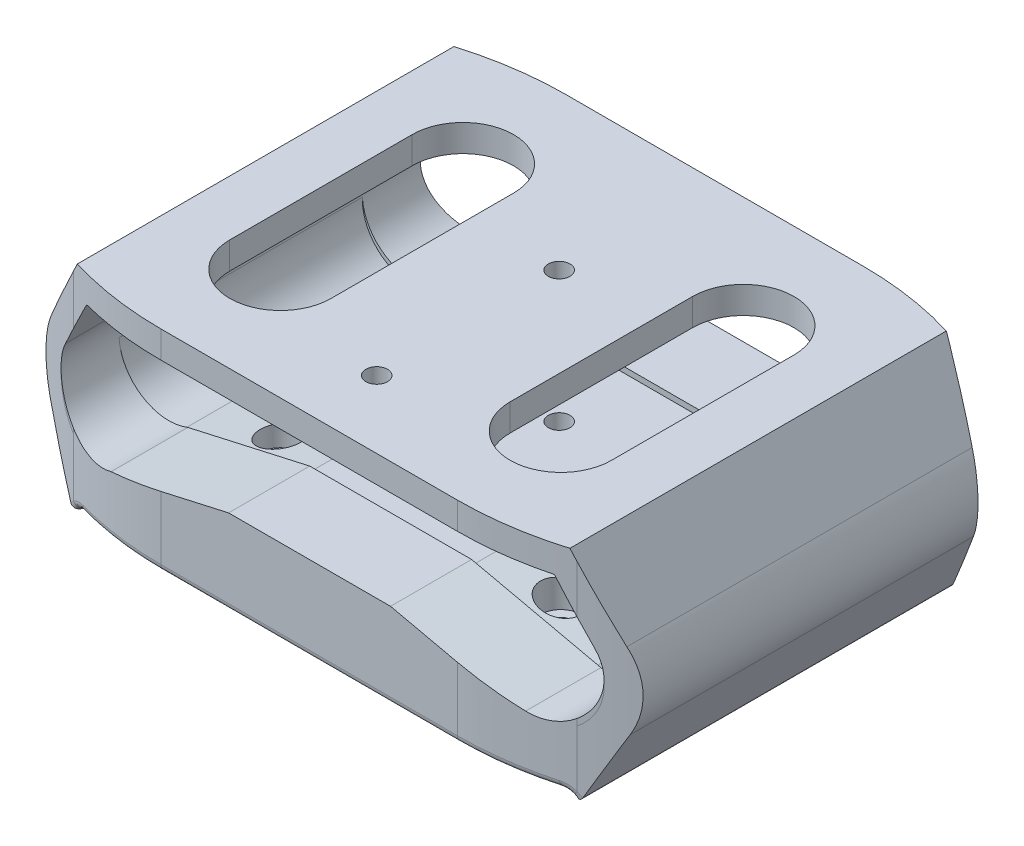
SolidWorks part; units mm, degrees
ref_plane "前视基准面" through (0, 0, 0) normal (0, 0, 1) x (1, 0, 0)
ref_plane "上视基准面" through (0, 0, 0) normal (0, 1, 0) x (1, 0, 0)
ref_plane "右视基准面" through (0, 0, 0) normal (1, 0, 0) x (0, 0, -1)
sketch "草图1" plane through (0, 0, 0) normal (0, 0, 1) x (1, 0, 0)
  line L6 (-36.4384, 98.3864) -> (-42.625, 87.564)
  line L10 (42.5656, 87.668) -> (36.4384, 98.3864)
  line L11 (36.4384, 98.3864) -> (-36.4384, 98.3864)
  line L12 (-34.1176, 94.3864) -> (-39.1524, 85.5789)
  line L13 (-31.105, 74.6866) -> (-11.9778, 78.9864)
  line L14 (-11.9778, 78.9864) -> (11.9778, 78.9864)
  line L15 (11.9778, 78.9864) -> (30.0087, 74.933)
  line L16 (39.118, 85.639) -> (34.1176, 94.3864)
  line L17 (34.1176, 94.3864) -> (-34.1176, 94.3864)
  line L18 (-34.1176, 94.3864) -> (-39.1524, 85.5789)
  line L19 (-31.105, 74.6866) -> (-11.9778, 78.9864)
  line L20 (-11.9778, 78.9864) -> (11.9778, 78.9864)
  line L21 (11.9778, 78.9864) -> (30.0087, 74.933)
  line L22 (39.118, 85.639) -> (34.1176, 94.3864)
  line L23 (34.1176, 94.3864) -> (-34.1176, 94.3864)
  line L24 (35, 67.1864) -> (21.943, 67.1864) construction
  line L25 (-21.943, 67.1864) -> (21.943, 67.1864) construction
  line L26 (-21.943, 67.1864) -> (-35, 67.1864) construction
  line L27 (35, 67.1864) -> (21.943, 67.1864)
  line L28 (-21.943, 67.1864) -> (21.943, 67.1864)
  line L29 (-21.943, 67.1864) -> (-35, 67.1864)
  line L30 (-37, 65.1864) -> (-42.8843, 76.7286)
  line L31 (37, 65.1864) -> (42.908, 76.5149)
  line L33 (-30.2277, 70.7839) -> (-11.5337, 74.9864) construction
  line L34 (-11.5337, 74.9864) -> (11.5337, 74.9864) construction
  line L35 (11.5337, 74.9864) -> (28.8425, 71.0953) construction
  arc A2 (-42.625, 87.564) -> (-42.8843, 76.7286) centre (-32.728, 81.9064) ccw
  arc A3 (42.908, 76.5149) -> (42.5656, 87.668) centre (32.8, 81.7864) ccw
  arc A4 (-39.1524, 85.5789) -> (-31.105, 74.6866) centre (-32.728, 81.9064) ccw
  arc A5 (30.0087, 74.933) -> (39.118, 85.639) centre (32.8, 81.7864) ccw
  arc A6 (-39.1524, 85.5789) -> (-31.105, 74.6866) centre (-32.728, 81.9064) ccw
  arc A7 (30.0087, 74.933) -> (39.118, 85.639) centre (32.8, 81.7864) ccw
  arc A8 (37, 65.1864) -> (35, 67.1864) centre (35, 65.1864) ccw construction
  arc A9 (-35, 67.1864) -> (-37, 65.1864) centre (-35, 65.1864) ccw construction
  arc A10 (37, 65.1864) -> (35, 67.1864) centre (35, 65.1864) ccw
  arc A11 (-35, 67.1864) -> (-37, 65.1864) centre (-35, 65.1864) ccw
  arc A12 (-42.625, 87.564) -> (-30.2277, 70.7839) centre (-32.728, 81.9064) ccw construction
  arc A13 (28.8425, 71.0953) -> (42.5656, 87.668) centre (32.8, 81.7864) ccw construction
  dimension "D1" = 0.2
  dimension "D2" = 4
extrude "凸台-拉伸1" add sketch "草图1" against normal up to surface (60 mm away)
sketch "草图2" plane through (0, 67.1864, 0) normal (0, -1, 0) x (1, 0, 0)
  line L1 (46.1297, -53.7608) -> (54.661, -49.0455) construction
  line L2 (46.1297, -53.7608) -> (54.661, -49.0455)
  line L3 (35, -60) -> (-35, -60) construction
  line L4 (21.943, -58) -> (21.943, -60) construction
  line L5 (54.661, -49.0455) -> (55.2201, -72.0519)
  line L6 (55.2201, -72.0519) -> (47.4236, -78.506)
  line L7 (47.4236, -78.506) -> (21.943, -68.9024)
  line L8 (21.943, -68.9024) -> (21.943, -60)
  line L12 (-47.4236, -78.506) -> (-21.943, -68.9024)
  line L13 (-55.2201, -72.0519) -> (-47.4236, -78.506)
  line L14 (-54.661, -49.0455) -> (-55.2201, -72.0519)
  line L15 (-46.1297, -53.7608) -> (-54.661, -49.0455)
  line L16 (-21.943, -68.9024) -> (-21.943, -60)
  line L19 (-55.2201, 12.0519) -> (-47.4236, 18.506)
  line L20 (-54.661, -10.9545) -> (-55.2201, 12.0519)
  line L21 (-46.1297, -6.2392) -> (-54.661, -10.9545)
  line L22 (-21.943, 8.9024) -> (-21.943, 0)
  line L23 (-47.4236, 18.506) -> (-21.943, 8.9024)
  line L24 (47.4236, 18.506) -> (21.943, 8.9024)
  line L25 (55.2201, 12.0519) -> (47.4236, 18.506)
  line L26 (54.661, -10.9545) -> (55.2201, 12.0519)
  line L27 (46.1297, -6.2392) -> (54.661, -10.9545)
  line L28 (21.943, 8.9024) -> (21.943, 0)
  arc A0 (37.2486, -57.5998) -> (21.943, -60) centre (21.943, -10) cw
  arc A1 (-37.2486, -57.5998) -> (-21.943, -60) centre (-21.943, -10) ccw
  arc A2 (-37.2486, -2.4002) -> (-21.943, 0) centre (-21.943, -50) cw
  arc A3 (37.2486, -2.4002) -> (21.943, 0) centre (21.943, -50) ccw
  spline S0 degree 3 poles (-1285.9943, 1433.6768) (-243.3632, -0.9152) (-26.08, -85.4419) (135.79, -14.9664) (-55.3237, 244.096) (509.0811, -1999.3449) knots -22.492359 -22.492359 -22.492359 -22.492359 0.5 0.5 32.253699 32.253699 32.253699 32.253699 only from (37.2486, -57.5998) to (46.1297, -53.7608) construction
  spline S1 degree 3 poles (37.2486, -57.5998) (38.8751, -57.0768) (40.4241, -56.4871) (43.3808, -55.1998) (44.7885, -54.502) (46.1297, -53.7608) knots 0 0 0 0 0.5 0.5 1 1 1 1
  spline S2 degree 3 poles (-37.2486, -57.5998) (-38.8751, -57.0768) (-40.4241, -56.4871) (-43.3808, -55.1998) (-44.7885, -54.502) (-46.1297, -53.7608) knots 0 0 0 0 0.5 0.5 1 1 1 1
  spline S3 degree 3 poles (-37.2486, -2.4002) (-38.8751, -2.9232) (-40.4241, -3.5129) (-43.3808, -4.8002) (-44.7885, -5.498) (-46.1297, -6.2392) knots 0 0 0 0 0.5 0.5 1 1 1 1
  spline S4 degree 3 poles (37.2486, -2.4002) (38.8751, -2.9232) (40.4241, -3.5129) (43.3808, -4.8002) (44.7885, -5.498) (46.1297, -6.2392) knots 0 0 0 0 0.5 0.5 1 1 1 1
extrude "切除-拉伸1" cut sketch "草图2" against normal mid plane 138
fillet "圆角1" radius 1 12 edges at (33.7286, 63.6425, -58.5912) (28.5289, 67.1864, -59.5644) (0, 67.1864, -60) (-36.4206, 66.5942, -57.8581) (33.5845, 63.7735, -1.3741) (28.5289, 67.1864, -0.4356) (0, 67.1864, 0) (-28.5289, 67.1864, -0.4356) (-28.5289, 67.1864, -59.5644) (37, 65.1864, -30) (-37, 65.1864, -30) (-36.7035, 66.2343, -2.2284)
sketch "草图4" plane through (0, 98.3864, 0) normal (0, 1, 0) x (1, 0, 0)
  line L0 (-20.7462, 43.5) -> (-20.7462, 16.5) construction
  line L1 (-13.2462, 43.5) -> (-13.2462, 16.5)
  line L2 (-28.2462, 43.5) -> (-28.2462, 16.5)
  line L3 (0, 66.5679) -> (0, 53.4321) construction
  line L4 (20.7462, 43.5) -> (20.7462, 16.5) construction
  line L5 (13.2462, 43.5) -> (13.2462, 16.5)
  line L6 (28.2462, 43.5) -> (28.2462, 16.5)
  arc A0 (-13.2462, 43.5) -> (-28.2462, 43.5) centre (-20.7462, 43.5) ccw
  arc A1 (-28.2462, 16.5) -> (-13.2462, 16.5) centre (-20.7462, 16.5) ccw
  arc A2 (13.2462, 43.5) -> (28.2462, 43.5) centre (20.7462, 43.5) cw
  arc A3 (28.2462, 16.5) -> (13.2462, 16.5) centre (20.7462, 16.5) cw
  point P4 (-20.7462, 30)
  point P13 (20.7462, 30)
extrude "切除-拉伸2" cut sketch "草图4" against normal blind 8
sketch "草图5" plane through (0, 98.3864, 0) normal (0, 1, 0) x (1, 0, 0)
  circle A0 centre (-20.7462, 43.5) radius 1.6
  circle A1 centre (-20.7462, 16.5) radius 1.6
  circle A2 centre (20.7462, 43.5) radius 1.6
  circle A3 centre (20.7462, 16.5) radius 1.6
extrude "切除-拉伸3" cut sketch "草图5" against normal blind 80
sketch "草图6" plane through (0, 98.3864, 0) normal (0, 1, 0) x (1, 0, 0)
  circle A0 centre (-20.7462, 43.5) radius 3
  circle A1 centre (20.7462, 43.5) radius 3
  circle A2 centre (-20.7462, 16.5) radius 3
  circle A3 centre (20.7462, 16.5) radius 3
extrude "切除-拉伸4" cut sketch "草图6" against normal blind 25
sketch "草图7" plane through (0, 98.3864, 0) normal (0, 1, 0) x (1, 0, 0)
  circle A0 centre (0, 37) radius 1.6
  circle A1 centre (0, 10) radius 1.6
extrude "切除-拉伸5" cut sketch "草图7" against normal blind 36
sketch "草图8" plane through (0, 0, 0) normal (0, 0, 1) x (1, 0, 0)
  line L0 (39.2149, 86.4342) -> (34.6646, 94.3864)
  line L1 (34.6646, 94.3864) -> (-34.5297, 94.3864)
  line L2 (-34.5297, 94.3864) -> (-39.0555, 86.4616)
  line L3 (-29.9417, 75.7594) -> (-11.9125, 79.8203)
  line L4 (-11.9125, 79.8203) -> (12.0431, 79.8303)
  line L5 (12.0431, 79.8303) -> (31.1721, 75.5385)
  arc A0 (-39.0555, 86.4616) -> (-40.1359, 82.6116) centre (-32.7359, 82.6116) ccw
  arc A1 (-40.1359, 82.6116) -> (-29.9417, 75.7594) centre (-32.7359, 82.6116) ccw
  arc A2 (31.1721, 75.5385) -> (39.2149, 86.4342) centre (32.7921, 82.759) ccw
extrude "切除-拉伸6" cut sketch "草图8" against normal mid plane 184
sketch "草图9" plane through (0, 0, 0) normal (0, 0, 1) x (1, 0, 0)
  line L15 (-29.9417, 75.7594) -> (-11.9125, 79.8203)
  line L16 (-11.9125, 79.8203) -> (12.0431, 79.8303)
  line L17 (12.0431, 79.8303) -> (31.1721, 75.5385)
  line L18 (30.0087, 74.933) -> (21.943, 76.7462) construction
  line L19 (11.9778, 78.9864) -> (21.943, 76.7462) construction
  line L20 (-11.9778, 78.9864) -> (11.9778, 78.9864) construction
  line L21 (-21.943, 76.7462) -> (-11.9778, 78.9864) construction
  line L22 (-21.943, 76.7462) -> (-31.105, 74.6866) construction
  line L23 (30.0087, 74.933) -> (21.943, 76.7462)
  line L24 (11.9778, 78.9864) -> (21.943, 76.7462)
  line L25 (-11.9778, 78.9864) -> (11.9778, 78.9864)
  line L26 (-21.943, 76.7462) -> (-11.9778, 78.9864)
  line L27 (-21.943, 76.7462) -> (-31.105, 74.6866)
  arc A7 (-40.1231, 82.1763) -> (-29.9417, 75.7594) centre (-32.7359, 82.6116) ccw
  arc A8 (31.1721, 75.5385) -> (40.1798, 82.333) centre (32.7921, 82.759) ccw
  arc A9 (37.2486, 75.8728) -> (40.1798, 82.333) centre (32.8, 81.7864) ccw construction
  arc A10 (30.0087, 74.933) -> (37.2486, 75.8728) centre (32.8, 81.7864) ccw construction
  arc A11 (-37.2486, 76.0477) -> (-31.105, 74.6866) centre (-32.728, 81.9064) ccw construction
  arc A12 (-40.1231, 82.1763) -> (-37.2486, 76.0477) centre (-32.728, 81.9064) ccw construction
  arc A13 (37.2486, 75.8728) -> (40.1798, 82.333) centre (32.8, 81.7864) ccw
  arc A14 (30.0087, 74.933) -> (37.2486, 75.8728) centre (32.8, 81.7864) ccw
  arc A15 (-37.2486, 76.0477) -> (-31.105, 74.6866) centre (-32.728, 81.9064) ccw
  arc A16 (-40.1231, 82.1763) -> (-37.2486, 76.0477) centre (-32.728, 81.9064) ccw
extrude "凸台-拉伸2" add sketch "草图9" against normal blind 12
ref_plane "基准面1" through (0, 0, -30) normal (0, 0, 1) x (1, 0, 0)
mirror "镜向1" about plane through (0, 0, -30) normal (0, 0, 1) of "凸台-拉伸2"
sketch "草图10" plane through (0, 98.3864, 0) normal (0, 1, 0) x (1, 0, 0)
  line L0 (-42.625, 55.522) -> (-42.625, 62.2093)
  line L1 (-42.625, 62.2093) -> (-21.943, 62.2093)
  line L2 (-21.943, 62.2093) -> (-21.943, 60)
  line L3 (0, 60) -> (0, 80.423) construction
  line L4 (-21.943, -2.2093) -> (-21.943, 0)
  line L5 (-21.943, 60) -> (21.943, 60) construction
  line L6 (36.4384, 30) -> (57.8591, 30) construction
  line L7 (36.4384, 57.8527) -> (36.4384, 2.1473) construction
  line L8 (21.943, 62.2093) -> (21.943, 60)
  line L9 (42.625, 62.2093) -> (21.943, 62.2093)
  line L10 (42.625, 55.522) -> (42.625, 62.2093)
  line L11 (-42.625, -2.2093) -> (-21.943, -2.2093)
  line L12 (-42.625, 4.478) -> (-42.625, -2.2093)
  line L14 (42.625, -2.2093) -> (21.943, -2.2093)
  line L15 (21.943, -2.2093) -> (21.943, 0)
  line L16 (42.5656, 4.451) -> (42.625, -2.2093)
  arc A0 (-36.4384, 57.8527) -> (-37.2486, 57.5998) centre (-21.943, 10) ccw construction
  arc A1 (-21.943, 60) -> (-36.4384, 57.8527) centre (-21.943, 10) ccw construction
  arc A2 (-36.4384, 57.8527) -> (-37.2486, 57.5998) centre (-21.943, 10) ccw
  arc A3 (-21.943, 60) -> (-36.4384, 57.8527) centre (-21.943, 10) ccw
  arc A4 (21.943, 60) -> (36.4384, 57.8527) centre (21.943, 10) cw
  arc A5 (36.4384, 57.8527) -> (37.2486, 57.5998) centre (21.943, 10) cw
  arc A6 (-21.943, 0) -> (-36.4384, 2.1473) centre (-21.943, 50) cw
  arc A7 (-36.4384, 2.1473) -> (-37.2486, 2.4002) centre (-21.943, 50) cw
  arc A10 (21.943, 0) -> (36.4384, 2.1473) centre (21.943, 50) ccw construction
  arc A11 (21.943, 0) -> (36.4384, 2.1473) centre (21.943, 50) ccw
  arc A13 (36.4384, 2.1473) -> (37.2486, 2.4002) centre (21.943, 50) ccw construction
  arc A14 (39.3375, -7.4233) -> (40.3097, -7.1197) centre (21.943, 50) ccw
  arc A15 (39.3375, -7.4233) -> (40.3097, -7.1197) centre (21.943, 50) ccw
  arc A16 (36.4384, 2.1473) -> (37.2486, 2.4002) centre (21.943, 50) ccw
  spline S0 degree 3 poles (-509.3202, 2000.2954) (55.3776, -244.1692) (-135.8033, 14.9606) (26.0795, 85.4416) (243.3598, 0.9165) (1285.9698, -1433.643) knots -31.258183 -31.258183 -31.258183 -31.258183 0.5 0.5 23.492178 23.492178 23.492178 23.492178 only from (-42.625, 55.522) to (-37.2486, 57.5998) construction
  spline S1 degree 3 poles (-42.625, 55.522) (-42.3861, 55.6306) (-42.1452, 55.7377) (-40.4241, 56.4871) (-38.8751, 57.0768) (-37.2486, 57.5998) knots 0.4179 0.4179 0.4179 0.4179 0.5 0.5 1 1 1 1
  spline S2 degree 3 poles (42.625, 55.522) (42.3861, 55.6306) (42.1452, 55.7377) (40.4241, 56.4871) (38.8751, 57.0768) (37.2486, 57.5998) knots 0.4179 0.4179 0.4179 0.4179 0.5 0.5 1 1 1 1
  spline S3 degree 3 poles (-42.625, 4.478) (-42.3861, 4.3694) (-42.1452, 4.2623) (-40.4241, 3.5129) (-38.8751, 2.9232) (-37.2486, 2.4002) knots 0.4179 0.4179 0.4179 0.4179 0.5 0.5 1 1 1 1
  spline S4 degree 3 poles (509.3045, -1940.233) (-55.3741, 304.1644) (135.8024, 45.039) (-26.0796, -25.4417) (-243.3604, 59.0837) (-1285.974, 1493.6488) knots -31.257889 -31.257889 -31.257889 -31.257889 0.5 0.5 23.492209 23.492209 23.492209 23.492209 only from (42.5656, 4.451) to (37.2486, 2.4002) construction
  spline S5 degree 3 poles (42.5656, 4.451) (42.3461, 4.3517) (42.1251, 4.2535) (40.4241, 3.5129) (38.8751, 2.9232) (37.2486, 2.4002) knots 0.424704 0.424704 0.424704 0.424704 0.5 0.5 1 1 1 1
  arc M26 (21.943, 0) -> (36.4384, 2.1473) centre (21.943, 50) ccw
  arc M28 (36.4384, 57.8527) -> (21.943, 60) centre (21.943, 10) ccw
  arc M30 (-21.943, 60) -> (-36.4384, 57.8527) centre (-21.943, 10) ccw
  arc M32 (-36.4384, 2.1473) -> (-21.943, 0) centre (-21.943, 50) ccw
  dimension "D1" = 10
extrude "切除-拉伸7" cut sketch "草图10" against normal mid plane 180 contours L0 S1 A2 L2 L1 M30 | S2 L10 L9 L8 A5 M28 | L16 S5 A16 L15 L14 M26 | S3 L12 L11 L4 A7 M32 region at (-34.3644, 98.3864, -60.133) region at (-34.3644, 98.3864, 0.133) region at (34.3644, 98.3864, -60.133) region at (34.3428, 98.3864, 0.1392)
